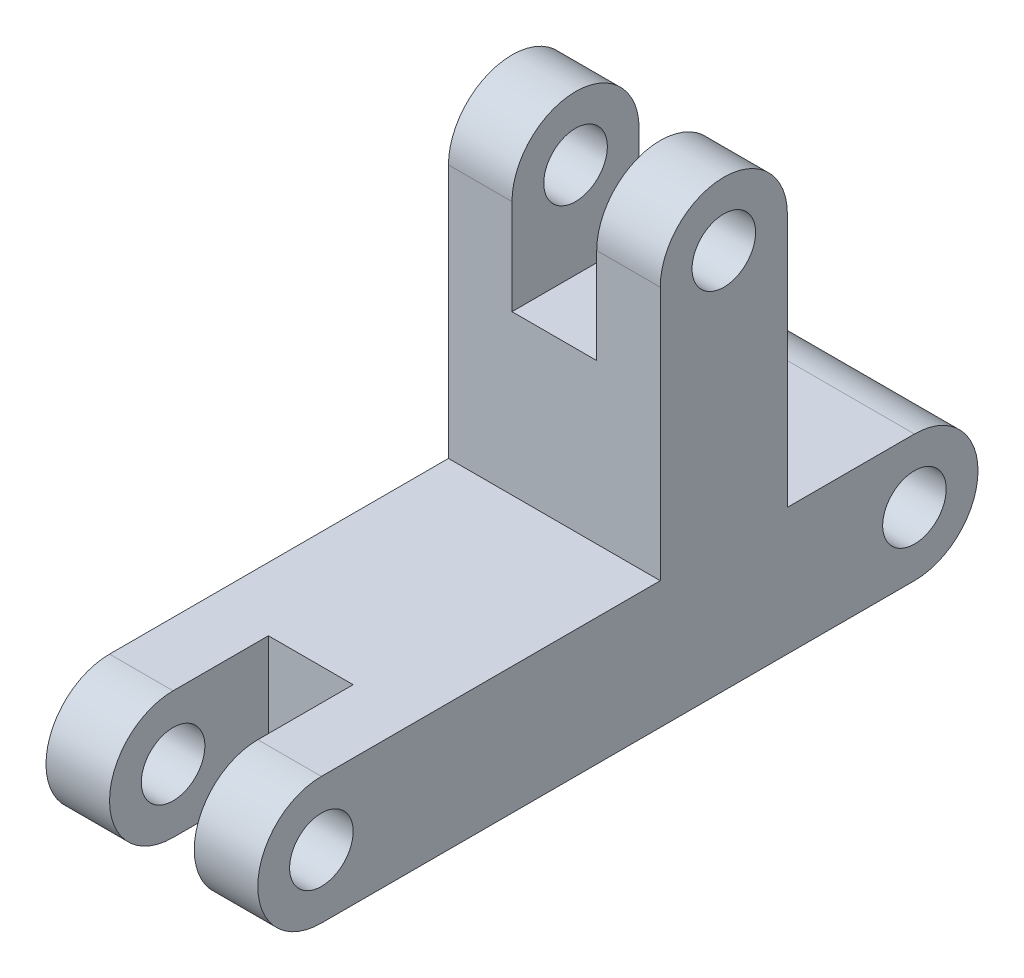
SolidWorks part; units mm, degrees
ref_plane "Alzado" through (0, 0, 0) normal (0, 0, 1) x (1, 0, 0)
ref_plane "Planta" through (0, 0, 0) normal (0, 1, 0) x (1, 0, 0)
ref_plane "Vista lateral" through (0, 0, 0) normal (1, 0, 0) x (0, 0, -1)
sketch "Croquis1" plane through (0, 0, 0) normal (1, 0, 0) x (0, 0, -1)
  line L0 (-14, 0) -> (14, 0) construction
  line L1 (-14, 3) -> (2, 3)
  line L2 (-14, -3) -> (14, -3)
  line L3 (8, 3) -> (14, 3)
  line L5 (2, 3) -> (2, 15)
  line L6 (2, 15) -> (8, 15) construction
  line L7 (8, 3) -> (8, 15)
  arc A0 (-14, 3) -> (-14, -3) centre (-14, 0) ccw
  arc A1 (14, -3) -> (14, 3) centre (14, 0) ccw
  circle A2 centre (14, 0) radius 1.5
  arc A3 (8, 15) -> (2, 15) centre (5, 15) ccw
  circle A4 centre (5, 15) radius 1.5
  circle A5 centre (-14, 0) radius 1.5
  point P3 (0, 0)
  dimension "D2" = 3
  dimension "D3" = 3
  dimension "D4" = 3
  dimension "D1" = 28
  dimension "D5" = 6
  dimension "D6" = 12
extrude "Saliente-Extruir1" add sketch "Croquis1" along normal mid plane 10
sketch "Croquis2" plane through (0, 0, 0) normal (1, 0, 0) x (0, 0, -1)
  line L0 (2, 15) -> (2, 3) construction
  line L1 (2, 10.5) -> (8, 10.5)
  line L2 (2, 10.5) -> (2, 18)
  line L3 (2, 18) -> (8, 18)
  line L4 (8, 10.5) -> (8, 18)
  line L5 (8, 3) -> (8, 15) construction
  line L6 (2, 3) -> (-14, 3) construction
  line L7 (-9.5, 3) -> (-17, 3)
  line L8 (-9.5, 3) -> (-9.5, -3)
  line L9 (-9.5, -3) -> (-17, -3)
  line L10 (-17, 3) -> (-17, -3)
  line L11 (-14, -3) -> (14, -3) construction
  arc A0 (8, 15) -> (2, 15) centre (5, 15) ccw construction
  arc A1 (-14, 3) -> (-14, -3) centre (-14, 0) ccw construction
  dimension "D1" = 7.5
  dimension "D2" = 7.5
extrude "Cortar-Extruir1" cut sketch "Croquis2" against normal mid plane 4
